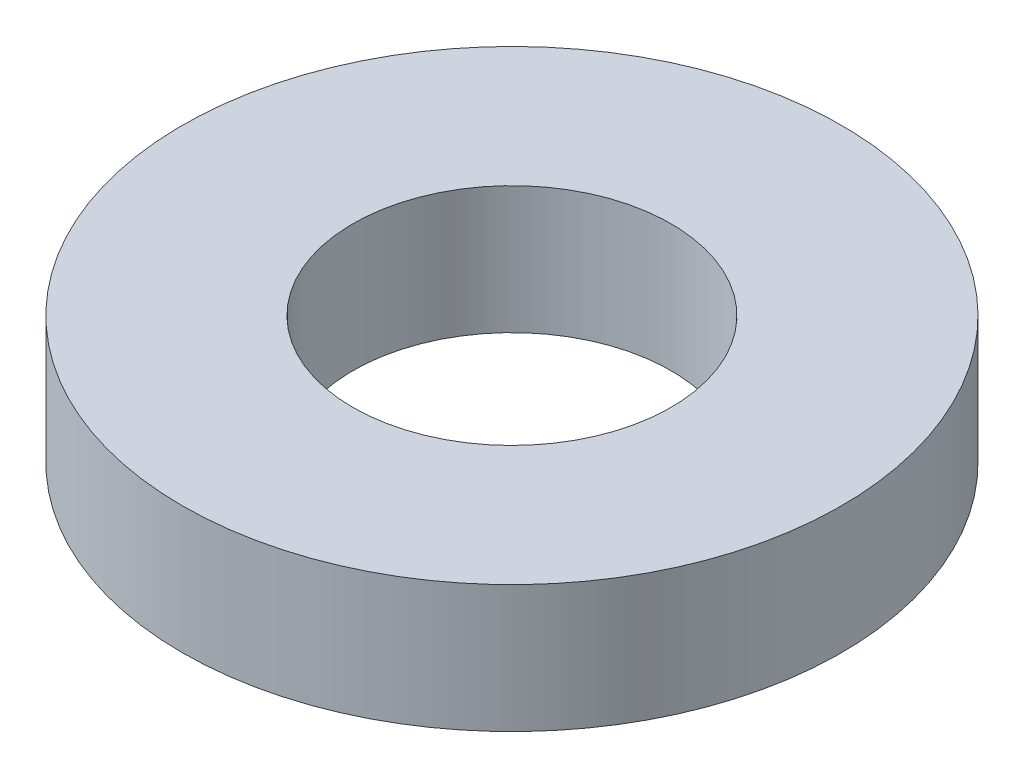
SolidWorks part; units mm, degrees
ref_plane "Front Plane" through (0, 0, 0) normal (0, 0, 1) x (1, 0, 0)
ref_plane "Top Plane" through (0, 0, 0) normal (0, 1, 0) x (1, 0, 0)
ref_plane "Right Plane" through (0, 0, 0) normal (1, 0, 0) x (0, 0, -1)
sketch "Sketch1" plane through (0, 0, 0) normal (0, 1, 0) x (1, 0, 0)
  circle A0 centre (0, 0) radius 72.5
  dimension "FLANGE_OD" = 145
extrude "Boss-Extrude1" add sketch "Sketch1" along normal blind 28
sketch "Sketch2" plane through (0, 0, 0) normal (0, 1, 0) x (1, 0, 0)
  circle A0 centre (0, 0) radius 35
  dimension "BORE_D" = 70
extrude "Cut-Extrude1" cut sketch "Sketch2" along normal through all
sketch "Sketch3" plane through (0, 28, 0) normal (0, 1, 0) x (1, 0, 0)
  circle A0 centre (0, 0) radius 20.3818 construction
  circle A1 centre (-20.3818, 0) radius 3.6353
  dimension "BOLT_D" = 7.2706
  dimension "BOLT_PCD" = 40.7636
extrude "Cut-Extrude2" cut sketch "Sketch3" against normal blind 23.6253 rebuild error yes
pattern_circular "CirPattern1" count 6 over 360 rebuild error yes
